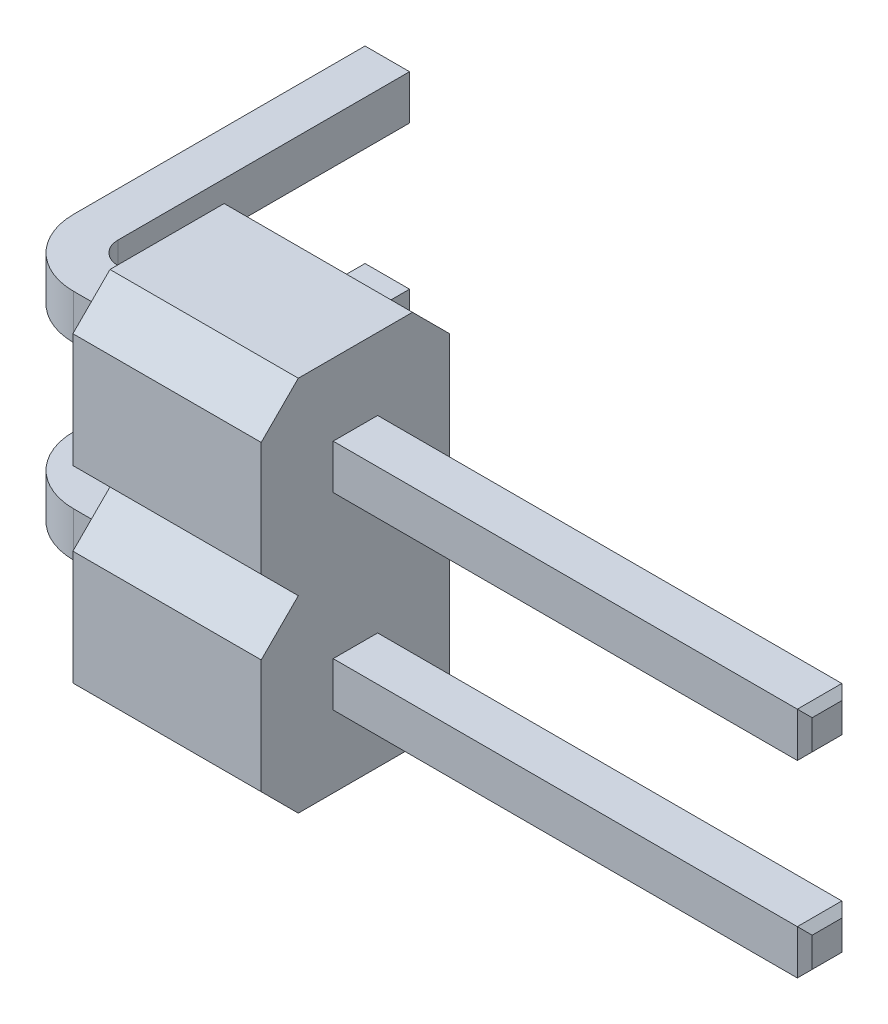
SolidWorks part; units mm, degrees
ref_plane "Front Plane" through (0, 0, 0) normal (0, 0, 1) x (1, 0, 0)
ref_plane "Top Plane" through (0, 0, 0) normal (0, 1, 0) x (1, 0, 0)
ref_plane "Right Plane" through (0, 0, 0) normal (1, 0, 0) x (0, 0, -1)
sketch "Sketch1" plane through (0, 0, 0) normal (1, 0, 0) x (0, 0, -1)
  line L0 (0, 0) -> (-1.27, 0) construction
  line L5 (-1.27, 0) -> (-1.27, 1.27) construction
  line L6 (-2.04, 1.27) -> (-0.5, 1.27)
  line L7 (-0.5, 1.27) -> (0, 0.77)
  line L8 (0, 0.77) -> (0, -0.77)
  line L9 (-2.54, 0.77) -> (-2.54, -0.77)
  line L10 (-2.04, 1.27) -> (-2.54, 0.77)
  line L11 (-0.5, -1.27) -> (0, -0.77)
  line L12 (-2.04, -1.27) -> (-0.5, -1.27)
  line L13 (-2.04, -1.27) -> (-2.54, -0.77)
  point P13 (-2.54, 0)
  dimension "D1" = 1.27
  dimension "D2" = 45
  dimension "D3" = 0.5
extrude "Plastic" add sketch "Sketch1" along normal blind 2.54
sketch "Sketch2" plane through (0, 0, 0) normal (0, 1, 0) x (1, 0, 0)
  line L0 (-1.56, 3.36) -> (-1.56, -0.67) construction
  line L1 (-0.96, -1.27) -> (8.9, -1.27) construction
  line L2 (0, -2.04) -> (0, -0.5) construction
  line L3 (-1.86, 3.36) -> (-1.86, -0.67)
  line L4 (-0.96, -1.57) -> (8.9, -1.57)
  line L5 (-1.26, 3.36) -> (-1.26, -0.67)
  line L6 (-0.96, -0.97) -> (8.9, -0.97)
  line L7 (-1.86, 3.36) -> (-1.26, 3.36)
  line L8 (8.9, -1.57) -> (8.9, -0.97)
  line L9 (2.54, -2.54) -> (0, -2.54) construction
  line L10 (2.54, -2.04) -> (2.54, -0.5) construction
  line L11 (0, -0.5) -> (0, 0) construction
  line L13 (2.54, -0.5) -> (2.54, 0) construction
  arc A0 (-1.56, -0.67) -> (-0.96, -1.27) centre (-0.96, -0.67) ccw construction
  arc A1 (-1.86, -0.67) -> (-0.96, -1.57) centre (-0.96, -0.67) ccw
  arc A2 (-1.26, -0.67) -> (-0.96, -0.97) centre (-0.96, -0.67) ccw
  point P5 (0, -1.27)
  point P28 (2.54, -0.25)
  dimension "D1" = 0.6
  dimension "D4" = 8.9
  dimension "D5" = 5.9
  dimension "D6" = 4.4
  dimension "D7" = 1.56
  dimension "D8" = 6.36
  dimension "D2" = 0.3
  dimension "D3" = 0.3
extrude "Contact" add sketch "Sketch2" along normal mid plane 0.6
chamfer "Chamfer1" distance 0.1 angle 45 8 edges at (8.9, 0.3, 1.27) (8.9, 0, 1.57) (8.9, -0.3, 1.27) (8.9, 0, 0.97) (-1.56, 0.3, -3.36) (-1.26, 0, -3.36) (-1.86, 0, -3.36) (-1.56, -0.3, -3.36)
pattern_linear "LPattern1" count 2 spacing 2.54 along (0, 1, 0) of "Plastic", "Contact", "Chamfer1"
sketch "Sketch3" plane through (0, 0, -3.36) normal (0, 0, -1) x (-1, 0, 0)
  line L0 (1.36, 0) -> (1.56, 0) construction
  line L1 (1.36, 0.2) -> (1.36, -0.2) construction
  line L2 (1.56, 0) -> (1.56, -0.2) construction
  line L3 (1.36, -0.2) -> (1.76, -0.2) construction
ref_axis "Axis1" through (-1.56, 0, -3.36) along (0, 0, 1)
